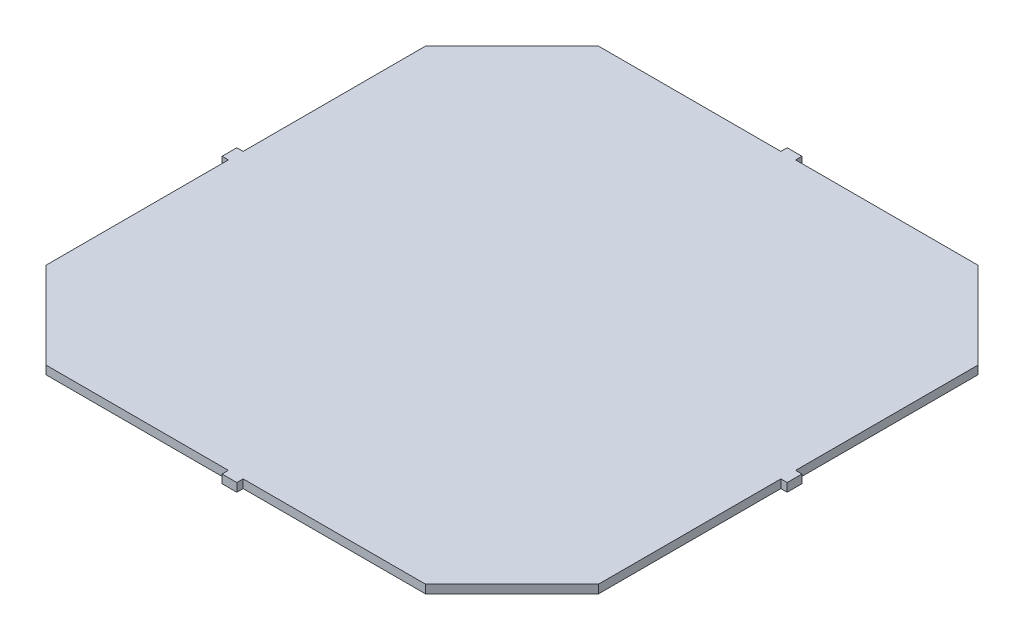
SolidWorks part; units mm, degrees
material "PETG"
ref_plane "Front Plane" through (0, 0, 0) normal (0, 0, 1) x (1, 0, 0)
ref_plane "Top Plane" through (0, 0, 0) normal (0, 1, 0) x (1, 0, 0)
ref_plane "Right Plane" through (0, 0, 0) normal (1, 0, 0) x (0, 0, -1)
sketch "Sketch1" plane through (0, 0, 0) normal (0, 1, 0) x (1, 0, 0)
  line L0 (-32.753, 22.5) -> (-22.5, 32.753)
  line L1 (-22.5, -32.753) -> (22.5, -32.753)
  line L2 (-32.753, -22.5) -> (-32.753, 22.5)
  line L3 (-22.5, 32.753) -> (22.5, 32.753)
  line L4 (32.753, -22.5) -> (32.753, 22.5)
  line L5 (-27.6265, -27.6265) -> (27.6265, 27.6265) construction
  line L6 (-27.6265, 27.6265) -> (27.6265, -27.6265) construction
  line L7 (-32.753, -22.5) -> (-22.5, -32.753)
  line L8 (22.5, -32.753) -> (32.753, -22.5)
  line L9 (22.5, 32.753) -> (32.753, 22.5)
  point P0 (0, 0)
  dimension "D1" = 45
  dimension "D2" = 45
  dimension "D3" = 135
  dimension "D4" = 135
  dimension "D5" = 14.5
  dimension "D6" = 135
extrude "Boss-Extrude1" add sketch "Sketch1" along normal blind 1
sketch "Sketch2" plane through (0, 1, 0) normal (0, 1, 0) x (1, 0, 0)
  line L0 (-32.753, 0) -> (32.753, 0) construction
  line L1 (-32.753, 22.5) -> (-32.753, -22.5) construction
  line L2 (32.753, -22.5) -> (32.753, 22.5) construction
  line L3 (0, 32.753) -> (0, -32.753) construction
  line L4 (22.5, 32.753) -> (-22.5, 32.753) construction
  line L5 (-22.5, -32.753) -> (22.5, -32.753) construction
  line L6 (33.503, 0.875) -> (33.503, -0.875)
  line L7 (-0.875, 32.753) -> (0.875, 32.753)
  line L8 (-0.875, 32.753) -> (-0.875, 33.503)
  line L9 (-0.875, 33.503) -> (0.875, 33.503)
  line L10 (0.875, 32.753) -> (0.875, 33.503)
  line L11 (-32.753, 0.875) -> (-33.503, 0.875)
  line L12 (-32.753, 0.875) -> (-32.753, -0.875)
  line L13 (-32.753, -0.875) -> (-33.503, -0.875)
  line L14 (-33.503, 0.875) -> (-33.503, -0.875)
  line L15 (32.753, -0.875) -> (33.503, -0.875)
  line L16 (32.753, 0.875) -> (32.753, -0.875)
  line L17 (32.753, 0.875) -> (33.503, 0.875)
  line L18 (0.875, -32.753) -> (0.875, -33.503)
  line L19 (-0.875, -33.503) -> (0.875, -33.503)
  line L20 (-0.875, -32.753) -> (-0.875, -33.503)
  line L21 (-0.875, -32.753) -> (0.875, -32.753)
  dimension "D1" = 1.75
  dimension "D2" = 0.75
  dimension "D3" = 1.75
  dimension "D4" = 0.75
extrude "Boss-Extrude2" add sketch "Sketch2" against normal blind 1
